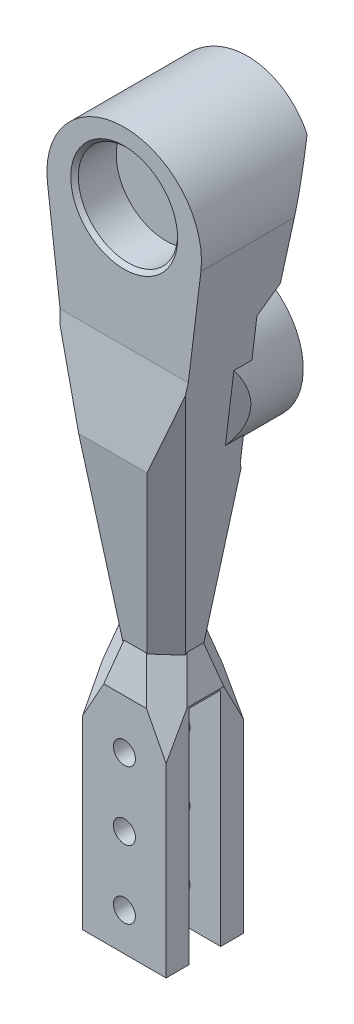
SolidWorks part; units mm, degrees
material "ABS"
ref_plane "Front Plane" through (0, 0, 0) normal (0, 0, 1) x (1, 0, 0)
ref_plane "Top Plane" through (0, 0, 0) normal (0, 1, 0) x (1, 0, 0)
ref_plane "Right Plane" through (0, 0, 0) normal (1, 0, 0) x (0, 0, -1)
sketch "Sketch1" plane through (0, 0, 0) normal (0, 0, 1) x (1, 0, 0)
  line L1 (-5.5, -14.75) -> (5.5, -14.75)
  line L2 (-5.5, -14.75) -> (-5.5, 14.75)
  line L3 (-5.5, 14.75) -> (5.5, 14.75)
  line L4 (5.5, -14.75) -> (5.5, 14.75)
  line L5 (-5.5, -14.75) -> (5.5, 14.75) construction
  line L6 (-5.5, 14.75) -> (5.5, -14.75) construction
  point P0 (0, 0)
  dimension "D1" = 11
  dimension "D2" = 29.5
extrude "Boss-Extrude1" add sketch "Sketch1" along normal blind 10.2
hole_wizard "CBORE for M2.5 SHCS1" positions "Sketch3" profile "Sketch4" counterbore size "M2.5" standard "ANSI Metric" end condition through all
sketch "Sketch3" plane through (0, 0, 0) normal (0, 0, -1) x (-1, 0, 0)
  line L0 (5.5, -14.75) -> (-5.5, -14.75) construction
  point P0 (0, -9.75)
  point P2 (0, -0.75)
  point P4 (0, 8.25)
  dimension "D1" = 9
  dimension "D2" = 5
  dimension "D3" = 9
sketch "Sketch4" plane through (0, -9.75, 0) normal (1, 0, 0) x (0, 1, 0)
  line L0 (0, 0) -> (0, 10.2)
  line L1 (0, 10.2) -> (1.45, 10.2)
  line L3 (1.45, 10.2) -> (1.45, 2.5)
  line L4 (2.75, 2.5) -> (1.45, 2.5)
  line L5 (2.75, 2.5) -> (2.75, 0.025)
  line L6 (2.75, 0.025) -> (2.775, 0)
  line L7 (2.775, 0) -> (0, 0)
  line L8 (-2.75, 0.025) -> (-2.775, 0) construction
  line L11 (0, -6.35) -> (0, 107.95) construction
  dimension "Thru Hole Dia." = 2.9
  dimension "Thru Hole Depth" = 10.2
  dimension "C'Bore Dia." = 5.5
  dimension "C'Bore Depth" = 2.5
  dimension "Near C'Sink Dia." = 5.55
  dimension "Near C'Sink Angle" = 90
sketch "Sketch5" plane through (-5.5, 0, 0) normal (-1, 0, 0) x (0, 0, 1)
  line L0 (10.2, -14.75) -> (0, -14.75) construction
  line L1 (3, -14.75) -> (7.2, -14.75)
  line L2 (3, -14.75) -> (3, 14.55)
  line L3 (3, 14.55) -> (7.2, 14.55)
  line L4 (7.2, -14.75) -> (7.2, 14.55)
  line L5 (0, 14.75) -> (0, -14.75) construction
  dimension "D1" = 4.2
  dimension "D2" = 3
  dimension "D3" = 29.3
extrude "Cut-Extrude1" cut sketch "Sketch5" against normal through all both and the other way through all
sketch "Sketch6" plane through (0, 14.75, 0) normal (0, 1, 0) x (1, 0, 0)
  line L4 (5.5, 0) -> (-5.5, 0)
  line L5 (-5.5, 0) -> (-5.5, -10.2)
  line L6 (-5.5, -10.2) -> (5.5, -10.2)
  line L7 (5.5, -10.2) -> (5.5, 0)
  line L8 (5.5, 0) -> (-5.5, 0)
  line L9 (-5.5, 0) -> (-5.5, -10.2)
  line L10 (-5.5, -10.2) -> (5.5, -10.2)
  line L11 (5.5, -10.2) -> (5.5, 0)
  dimension "D1" = 0
extrude "Boss-Extrude2" add sketch "Sketch6" along normal blind 5 draft 15
sketch "Sketch7" plane through (0, 19.75, 0) normal (0, 1, 0) x (1, 0, 0)
  line L4 (4.1603, -8.8603) -> (4.1603, -1.3397)
  line L5 (4.1603, -1.3397) -> (-4.1603, -1.3397)
  line L6 (-4.1603, -1.3397) -> (-4.1603, -8.8603)
  line L7 (-4.1603, -8.8603) -> (4.1603, -8.8603)
  line L8 (4.1603, -8.8603) -> (4.1603, -1.3397)
  line L9 (4.1603, -1.3397) -> (-4.1603, -1.3397)
  line L10 (-4.1603, -1.3397) -> (-4.1603, -8.8603)
  line L11 (-4.1603, -8.8603) -> (4.1603, -8.8603)
  dimension "D1" = 0
extrude "Boss-Extrude3" add sketch "Sketch7" along normal blind 60 draft 7
chamfer "Chamfer1" distance 2.5 angle 45 8 edges at (-7.8438, 49.75, -2.3438) (7.8438, 49.75, -2.3438) (7.8438, 49.75, 12.5438) (-7.8438, 49.75, 12.5438) (4.8301, 17.25, 0.6699) (4.8301, 17.25, 9.5301) (-4.8301, 17.25, 9.5301) (-4.8301, 17.25, 0.6699)
fillet "Fillet1" radius 10.1985 8 edges at (-11.5273, 79.75, 5.1191) (-0.0191, 79.75, -6.0273) (0.0191, 79.75, 16.2273) (11.5273, 79.75, 5.0809) (-10.249, 79.75, 14.9681) (10.2681, 79.75, 14.949) (10.249, 79.75, -4.7681) (-10.2681, 79.75, -4.749)
sketch "Sketch8" plane through (5.5, 0, 0) normal (1, 0, 0) x (0, 0, -1)
  line L0 (-10.2273, 79.75) -> (-10.2273, 54.75)
  line L2 (-10.2273, 54.75) -> (-11.7459, 43.2521)
  line L3 (-8.8499, 19.6653) -> (-15.675, 75.2521) construction
  line L4 (-11.7459, 43.2521) -> (-15.675, 75.2521)
  line L5 (-15.675, 75.2521) -> (-16.2273, 79.75)
  line L6 (-16.2273, 79.75) -> (-10.2273, 79.75)
  dimension "D1" = 25
  dimension "D2" = 32
  dimension "D3" = 6
extrude "Cut-Extrude2" cut sketch "Sketch8" against normal through all both and the other way through all
sketch "Sketch9" plane through (0, 0, 10.2273) normal (0, 0, 1) x (1, 0, 0)
  circle A0 centre (0, 70.5515) radius 6.55
  arc A3 (10.1225, 68.3086) -> (-10.1225, 68.3086) centre (0, 69.5515) ccw construction
  dimension "D1" = 13.1
  dimension "D2" = 1
extrude "Cut-Extrude3" cut sketch "Sketch9" against normal blind 5.5
chamfer "Chamfer2" distance 0.5 angle 45 1 edges at (6.55, 70.5515, 10.2273)
sketch "Sketch12" plane through (5.5, -0.3722, 0) normal (1, 0, 0) x (0, 0, -1)
  line L1 (0.4478, 34.6808) -> (4.0086, 63.6808)
  line L2 (-1.6053, 58.6808) -> (-1.6053, 40.6808)
  line L5 (2.104, 68.6808) -> (-10.2273, 68.6808) construction
  line L6 (-1.3501, 20.0375) -> (5.475, 75.6242) construction
  line L8 (-1.6053, 40.6808) -> (0.4478, 34.6808)
  line L9 (-1.6053, 58.6808) -> (4.0086, 63.6808)
  line L10 (-1.6053, 58.6808) -> (3.3947, 58.6808) construction
  dimension "D1" = 5
  dimension "D2" = 18
  dimension "D3" = 6
  dimension "D4" = 10
  dimension "D5" = 5
extrude "Cut-Extrude5" cut sketch "Sketch12" against normal through all both and the other way through all
sketch "Sketch13" plane through (0, 0, 1.6053) normal (0, 0, -1) x (-1, 0, 0)
  line L0 (-14.0006, 49.3086) -> (12.4586, 49.3086) construction
  line L2 (8.8947, 58.3086) -> (-8.8947, 58.3086) construction
  line L3 (6.6845, 40.3086) -> (-6.6845, 40.3086) construction
  circle A0 centre (0, 49.3086) radius 6.55
  circle A1 centre (0, 49.3086) radius 9
  dimension "D1" = 18
  dimension "D2" = 13.1
extrude "Boss-Extrude5" add sketch "Sketch13" along normal blind 6
chamfer "Chamfer5" distance 2 angle 50 2 edges at (-7.6739, 48.3664, 1.6053) (7.6739, 48.3664, 1.6053)
chamfer "Chamfer7" distance 0.5 angle 45 1 edges at (0, 55.8586, -4.3947)
